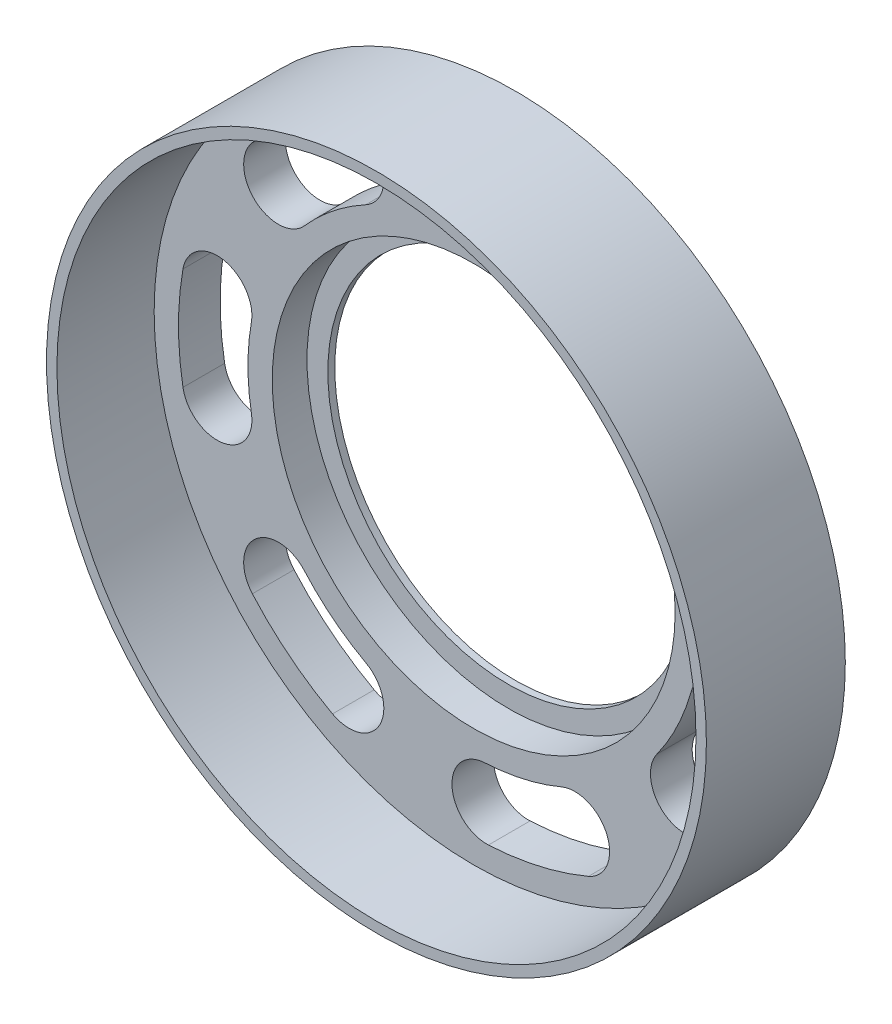
SolidWorks part; units mm, degrees
note: The reader was unsure of these and kept them because the rebuilt part matched: shared geometry of "Sketch1<5>", "Sketch1<7>".
ref_plane "Front Plane" through (0, 0, 0) normal (0, 0, 1) x (1, 0, 0)
ref_plane "Top Plane" through (0, 0, 0) normal (0, 1, 0) x (1, 0, 0)
ref_plane "Right Plane" through (0, 0, 0) normal (1, 0, 0) x (0, 0, -1)
sketch "Sketch1" plane through (0, 0, 0) normal (0, 0, 1) x (1, 0, 0)
  line L2 (0, 0) -> (-77.7202, 0) construction
  line L3 (0, 0) -> (-86.485, 15.2496) construction
  circle A0 centre (0, 0) radius 29
  circle A1 centre (0, 0) radius 47.5
  circle A4 centre (0, 0) radius 46
  circle A5 centre (0, 0) radius 32.5 construction
  circle A6 centre (0, 0) radius 42.5 construction
  arc A7 (-41.8543, 7.38) -> (-32.0063, 5.6436) centre (-36.9303, 6.5118) cw
  arc A8 (-41.8543, -7.38) -> (-32.0063, -5.6436) centre (-36.9303, -6.5118) ccw
  arc A9 (-41.8543, 7.38) -> (-41.8543, -7.38) centre (0, 0) ccw
  arc A10 (-32.0063, 5.6436) -> (-32.0063, -5.6436) centre (0, 0) ccw
  arc A11 (-15.5433, 28.5422) -> (-24.3679, 21.5048) centre (0, 0) ccw
  arc A12 (-31.8657, 28.1216) -> (-24.3679, 21.5048) centre (-28.1168, 24.8132) ccw
  arc A13 (-20.3258, 37.3244) -> (-31.8657, 28.1216) centre (0, 0) ccw
  arc A14 (-20.3258, 37.3244) -> (-15.5433, 28.5422) centre (-17.9345, 32.9333) cw
  arc A15 (12.6241, 29.948) -> (1.62, 32.4596) centre (0, 0) ccw
  arc A16 (2.1185, 42.4472) -> (1.62, 32.4596) centre (1.8692, 37.4534) ccw
  arc A17 (16.5085, 39.1627) -> (2.1185, 42.4472) centre (0, 0) ccw
  arc A18 (16.5085, 39.1627) -> (12.6241, 29.948) centre (14.5663, 34.5554) cw
  arc A19 (31.2853, 8.8023) -> (26.388, 18.9717) centre (0, 0) ccw
  arc A20 (34.5074, 24.8091) -> (26.388, 18.9717) centre (30.4477, 21.8904) ccw
  arc A21 (40.9115, 11.5107) -> (34.5074, 24.8091) centre (0, 0) ccw
  arc A22 (40.9115, 11.5107) -> (31.2853, 8.8023) centre (36.0984, 10.1565) cw
  arc A23 (26.388, -18.9717) -> (31.2853, -8.8023) centre (0, 0) ccw
  arc A24 (40.9115, -11.5107) -> (31.2853, -8.8023) centre (36.0984, -10.1565) ccw
  arc A25 (34.5074, -24.8091) -> (40.9115, -11.5107) centre (0, 0) ccw
  arc A26 (34.5074, -24.8091) -> (26.388, -18.9717) centre (30.4477, -21.8904) cw
  arc A27 (1.62, -32.4596) -> (12.6241, -29.948) centre (0, 0) ccw
  arc A28 (16.5085, -39.1627) -> (12.6241, -29.948) centre (14.5663, -34.5554) ccw
  arc A29 (2.1185, -42.4472) -> (16.5085, -39.1627) centre (0, 0) ccw
  arc A30 (2.1185, -42.4472) -> (1.62, -32.4596) centre (1.8692, -37.4534) cw
  arc A31 (-24.3679, -21.5048) -> (-15.5433, -28.5422) centre (0, 0) ccw
  arc A32 (-20.3258, -37.3244) -> (-15.5433, -28.5422) centre (-17.9345, -32.9333) ccw
  arc A33 (-31.8657, -28.1216) -> (-20.3258, -37.3244) centre (0, 0) ccw
  arc A34 (-31.8657, -28.1216) -> (-24.3679, -21.5048) centre (-28.1168, -24.8132) cw
  circle A35 centre (0, 0) radius 26
  dimension "D1" = 58
  dimension "D2" = 95
  dimension "D3" = 3
  dimension "D5" = 85
  dimension "D6" = 65
  dimension "D7" = 10
  dimension "D8" = 7
  dimension "D4" = 1.5
extrude "Boss-Extrude1" add sketch "Sketch1" along normal blind 20 contours A1 A4
extrude "Boss-Extrude2" add sketch "Sketch1<5>" along normal blind 6 contours A4 A35
sketch "Sketch1<5>" plane through (0, 0, 0) normal (0, 0, 1) x (1, 0, 0) same geometry as "Sketch1"
extrude "Boss-Extrude4" add sketch "Sketch1<7>" along normal blind 1 contours A0 A35
sketch "Sketch1<7>" plane through (0, 0, 0) normal (0, 0, 1) x (1, 0, 0) same geometry as "Sketch1"
